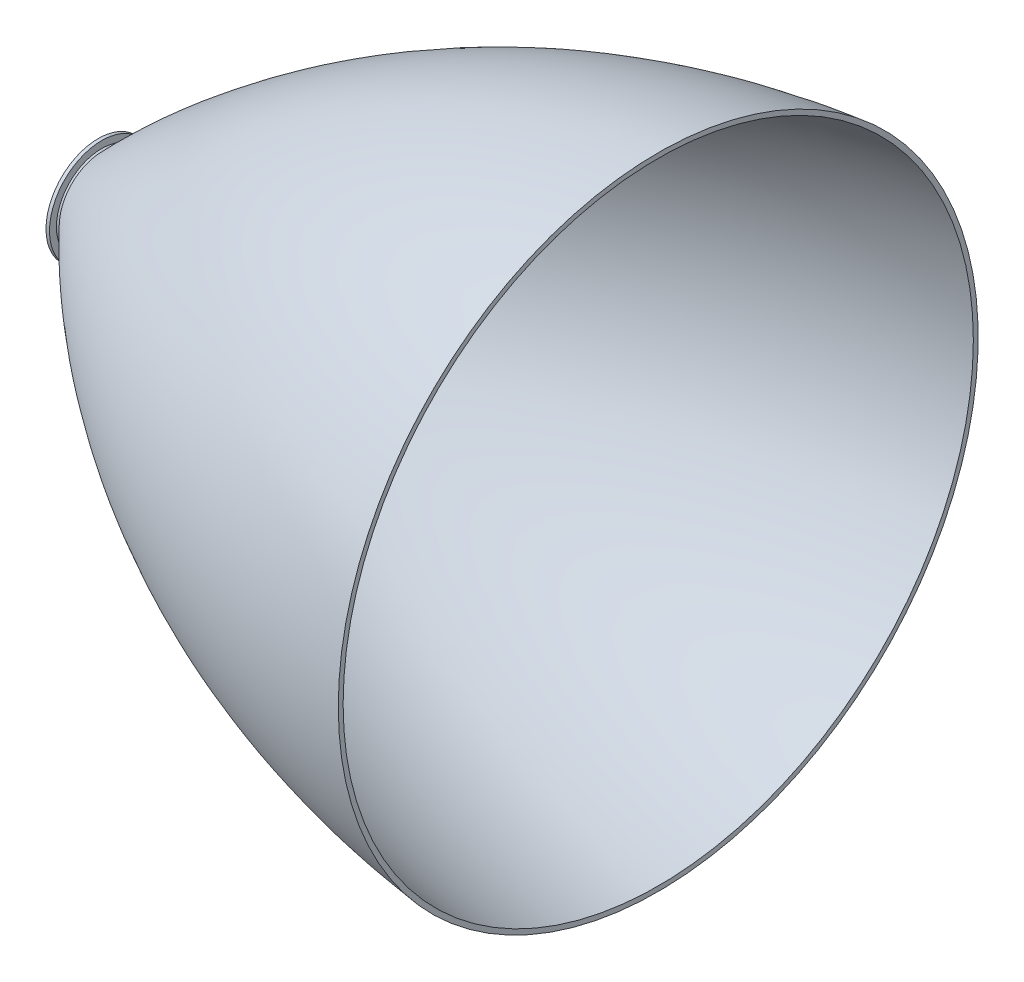
SolidWorks part; units mm, degrees
material "A286 Iron Base Superalloy"
ref_plane "Front Plane" through (0, 0, 0) normal (0, 0, 1) x (1, 0, 0)
ref_plane "Top Plane" through (0, 0, 0) normal (0, 1, 0) x (1, 0, 0)
ref_plane "Right Plane" through (0, 0, 0) normal (1, 0, 0) x (0, 0, -1)
sketch "Sketch1" plane through (0, 0, 0) normal (0, 0, 1) x (1, 0, 0)
  line L0 (-1229.8282, 0) -> (1426.3964, 0) construction
  line L1 (0, -70.104) -> (0, 70.104) construction
  line L2 (0, 0) -> (1016, 0) construction
  line L3 (1016, -576) -> (1016, 576) construction
  line L5 (1016, 584.89) -> (1016, 576)
  line L6 (0, -78.994) -> (0, -70.104)
  line L7 (1016, -584.89) -> (1016, -576)
  line L8 (-412.8242, -144.8099) -> (-412.8242, 144.8099) construction
  line L9 (-412.8242, 144.8099) -> (-412.8242, 153.6999)
  line L10 (-412.8242, -144.8099) -> (-412.8242, -153.6999)
  spline S0 degree 2 poles (0, 70.104) (423.6057, 493.6692) (1016, 576) knots 0 0 0 1 1 1
  spline S1 degree 2 poles (0, -70.104) (423.6057, -493.6692) (1016, -576) knots 0 0 0 1 1 1
  spline S2 degree 2 poles (0, -78.994) (417.2586, -516.0072) (1016, -584.89) knots 0 0 0 1 1 1
  spline S3 degree 2 poles (0, -70.104) (423.6057, -493.6692) (1016, -576) knots 0 0 0 1 1 1
  spline S4 degree 2 poles (0, 78.994) (417.2586, 516.0072) (1016, 584.89) knots 0 0 0 1 1 1
  spline S5 degree 2 poles (0, 70.104) (-195.4497, 157.4108) (-412.8242, 144.8099) knots 0 0 0 1 1 1
  spline S6 degree 2 poles (0, -70.104) (-195.4497, -157.4108) (-412.8242, -144.8099) knots 0 0 0 1 1 1
  spline S7 degree 2 poles (0, -78.994) (-192.7304, -176.7061) (-412.8242, -153.6999) knots 0 0 0 1 1 1
  spline S9 degree 2 poles (0, 78.994) (-192.7304, 176.7061) (-412.8242, 153.6999) knots 0 0 0 1 1 1
  point P8 (0, 0)
  point P14 (1016, 0)
  point P22 (-412.8242, 0)
  point P23 (595.566, 441.4595)
  point P27 (595.566, 429.4836)
  point P29 (473.8042, 429.4836)
  point P30 (473.8042, 412.3184)
  dimension "D4" = 8.89
  dimension "D1" = 140.208
  dimension "D2" = 1016
  dimension "D3" = 1152
  dimension "D5" = 8.89
  dimension "D6" = 8.89
  dimension "D7" = 289.6197
revolve "Revolve3" add sketch "Sketch1" angle 360 about L0 region at (312.3677, 330.251, 0)
ref_plane "Plane1" through (0, 0, 0) normal (1, 0, 0) x (0, 0, -1)
ref_plane "Plane2" through (-7.62, 0, 0) normal (-1, 0, 0) x (0, 0, 1)
sketch "Sketch4" plane through (-7.62, 0, 0) normal (-1, 0, 0) x (0, 0, 1)
  line L1 (-1213.2286, 638.9142) -> (1085.9115, 638.9142)
  line L2 (-1213.2286, 638.9142) -> (-1213.2286, -445.9528)
  line L3 (-1213.2286, -445.9528) -> (1085.9115, -445.9528)
  line L4 (1085.9115, 638.9142) -> (1085.9115, -445.9528)
extrude "Cut-Extrude1" cut sketch "Sketch4" along normal blind 554.228
sketch "Sketch5" plane through (-7.62, 0, 0) normal (-1, 0, 0) x (0, 0, 1)
  circle A0 centre (0, 0) radius 95.5048
  circle A1 centre (0, 0) radius 82.8048 construction
  circle A2 centre (0, 0) radius 82.8048
  dimension "D1" = 12.7
extrude "Boss-Extrude1" add sketch "Sketch5" against normal blind 6.35 separate body
